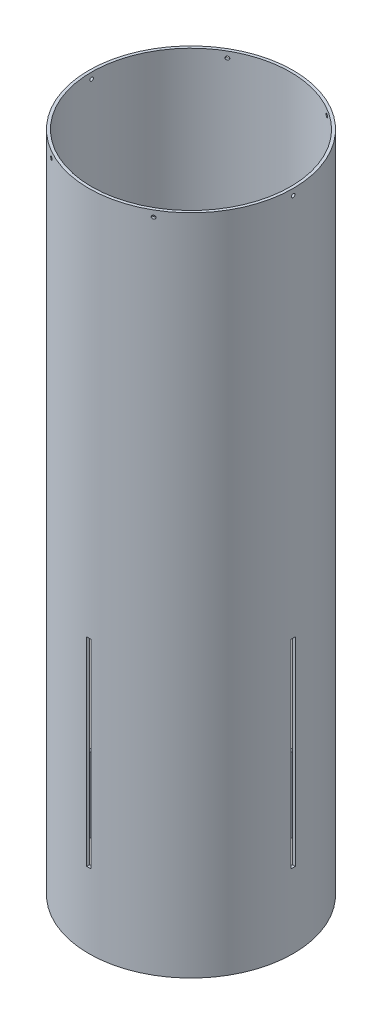
SolidWorks part; units mm, degrees
ref_plane "Front Plane" through (0, 0, 0) normal (0, 0, 1) x (1, 0, 0)
ref_plane "Top Plane" through (0, 0, 0) normal (0, 1, 0) x (1, 0, 0)
ref_plane "Right Plane" through (0, 0, 0) normal (1, 0, 0) x (0, 0, -1)
sketch "Sketch1" plane through (0, 0, 0) normal (0, 1, 0) x (1, 0, 0)
  circle A0 centre (0, 0) radius 76.2
  circle A1 centre (0, 0) radius 78.359
  dimension "D1" = 152.4
  dimension "D2" = 156.718
extrude "Boss-Extrude1" add sketch "Sketch1" along normal blind 508
ref_plane "Plane1" through (0, 0, 0) normal (0.7071, 0, 0.7071) x (0.7071, 0, -0.7071)
ref_axis "Axis1" through (0, 508, 0) along (0, -1, 0)
sketch "Sketch2" plane through (0, 0, 0) normal (1, 0, 0) x (0, 0, -1)
  line L0 (0, 0) -> (0, 57.15)
  line L1 (1.5875, 57.15) -> (-1.5875, 57.15)
  line L2 (1.5875, 57.15) -> (1.5875, 209.55)
  line L3 (1.5875, 209.55) -> (-1.5875, 209.55)
  line L4 (-1.5875, 57.15) -> (-1.5875, 209.55)
  line L5 (1.5875, 57.15) -> (-1.5875, 209.55) construction
  line L6 (1.5875, 209.55) -> (-1.5875, 57.15) construction
  line L7 (78.359, 508) -> (-78.359, 508) construction
  line L8 (78.359, 508) -> (-78.359, 508)
  line L9 (0, 508) -> (0, 503.2375)
  circle A0 centre (0, 503.2375) radius 1.3525
  point P0 (0, 133.35)
  dimension "D4" = 2.7051
  dimension "D1" = 3.175
  dimension "D2" = 152.4
  dimension "D3" = 57.15
  dimension "D5" = 4.7625
extrude "Cut-Extrude1" cut sketch "Sketch2" against normal through all contours L4 L1 L2 L3 region at (0, 133.35, 0)
pattern_circular "CirPattern1" count 4 over 360 about axis through (0, 0, 0) along (0, 1, 0) of "Cut-Extrude1" reverse direction yes
extrude "Cut-Extrude2" cut sketch "Sketch2<3>" against normal through all contours A0 region at (0, 502.3082, 0.9293)
sketch "Sketch2<3>" plane through (0, 0, 0) normal (1, 0, 0) x (0, 0, -1) same geometry as "Sketch2"
pattern_circular "CirPattern2" count 6 over 360 about axis through (0, 508, 0) along (0, -1, 0) of "Cut-Extrude2"
sketch "Sketch3" plane through (0, 0, 0) normal (0.7071, 0, 0.7071) x (0.7071, 0, -0.7071)
  line L0 (0, 0) -> (0, 127) construction
  circle A0 centre (0, 127) radius 3.175
  dimension "D1" = 6.35
  dimension "D2" = 127
extrude "Cut-Extrude3" cut sketch "Sketch3" against normal through all
equation "\"Aft_Lower_Length\"= 20in"
equation "\"D1@Boss-Extrude1\"=\"Aft_Lower_Length\""
equation "\"AB_Coupler_OD_Length\"= 1in"
equation "\"AB_Coupling_Section_Length\"= 0.375in"
equation "\"AB_Coupler_Length\"= \"AB_Coupler_OD_Length\" + \"AB_Coupling_Section_Length\" * 2"
equation "\"AB_Coupler_Num_Screws\"= 6"
equation "\"AB_Coupling_Screw_Diameter\"= 0.1065in"
equation "\"Aft_Upper_Length\"= \"Aft_Section_Length\" - \"Aft_Lower_Length\" - \"AB_Coupler_OD_Length\""
equation "\"Aft_Section_Length\"= 40in"
equation "\"D4@Sketch2\"=\"AB_Coupling_Screw_Diameter\""
equation "\"D5@Sketch2\"=\"AB_Coupling_Section_Length\"/2"
equation "\"D1@CirPattern2\"=\"AB_Coupler_Num_Screws\""
equation "\"Rail_Nut_From_Bottom\"= 5in"
equation "\"Rail_Nut_Diam\"= 0.25in"
equation "\"D1@Sketch3\"=\"Rail_Nut_Diam\""
equation "\"D2@Sketch3\"=\"Rail_Nut_From_Bottom\""
